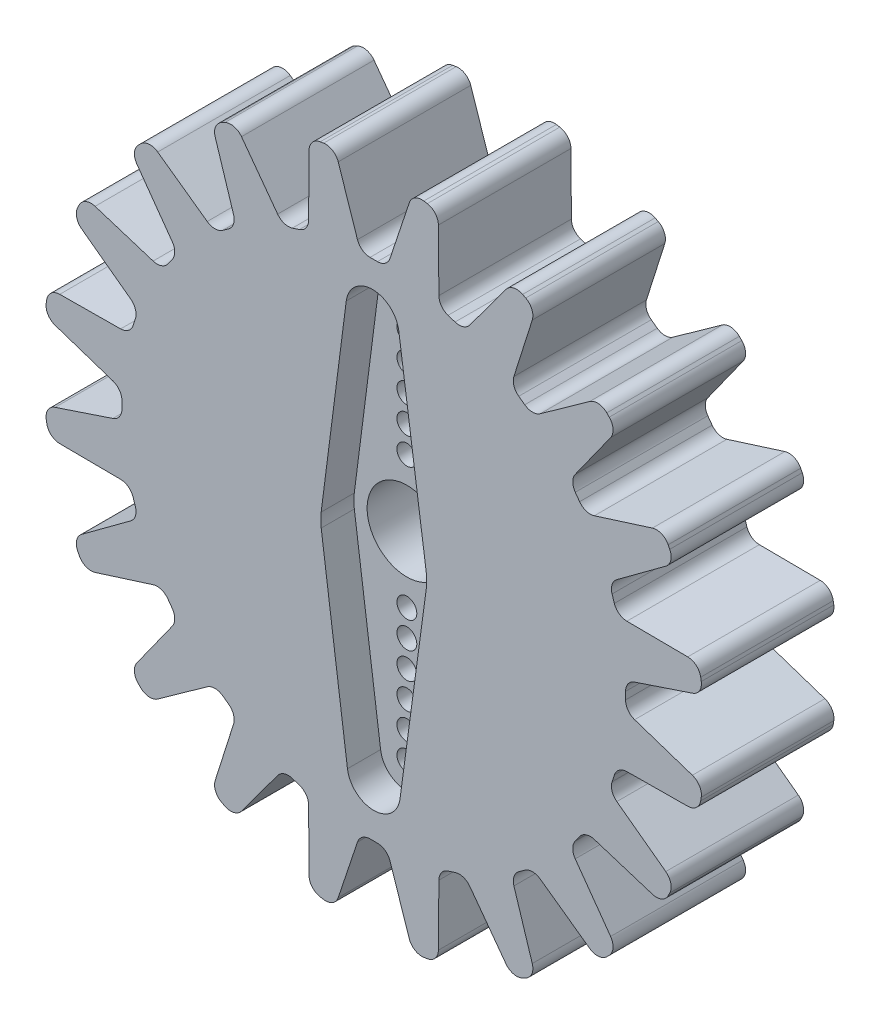
SolidWorks part; units mm, degrees
ref_plane "Front Plane" through (0, 0, 0) normal (0, 0, 1) x (1, 0, 0)
ref_plane "Top Plane" through (0, 0, 0) normal (0, 1, 0) x (1, 0, 0)
ref_plane "Right Plane" through (0, 0, 0) normal (1, 0, 0) x (0, 0, -1)
sketch "Sketch1" plane through (0, 0, 0) normal (0, 0, 1) x (1, 0, 0)
  circle A0 centre (0, 0) radius 25
  dimension "D1" = 50
extrude "Boss-Extrude1" add sketch "Sketch1" along normal blind 10
sketch "Sketch4" plane through (0, 0, 10) normal (0, 0, 1) x (1, 0, 0)
  line L0 (0, 25) -> (0, 19)
  line L1 (-1, 19) -> (1, 19)
  line L2 (-3, 25) -> (3, 25)
  line L3 (-3, 25) -> (-1, 19)
  line L4 (1, 19) -> (3, 25)
  circle A0 centre (0, 0) radius 25 construction
  point P9 (0, 19)
  point P12 (0, 25)
  point P13 (0, 25)
  circle M4 centre (0, 0) radius 25
  dimension "D1" = 6
  dimension "D2" = 2
  dimension "D3" = 6
extrude "Cut-Extrude1" cut sketch "Sketch4" against normal blind 15 contours L3 L1 L0 M4 | L1 L4 L0 M4 region at (1.0664, 22.4637, 10) region at (-1.0664, 22.4637, 10)
ref_axis "Axis1" through (0, 0, 10) along (0, 0, -1)
fillet "Fillet2" radius 1 4 edges at (1, 19, 5) (-1, 19, 5) (2.9421, 24.8263, 5) (-2.9421, 24.8263, 5)
pattern_circular "CirPattern3" count 20 over 360 about axis through (0, 0, 10) along (0, 0, -1) of "Fillet2", "Cut-Extrude1"
sketch "Sketch9" plane through (0, 0, 10) normal (0, 0, 1) x (1, 0, 0)
  circle A0 centre (0, 0) radius 22
sketch "Sketch10" plane through (0, 0, 10) normal (0, 0, 1) x (1, 0, 0)
  line L0 (1.8908, 15.2783) -> (3.961, 0.557)
  line L1 (-3.9643, -0.5333) -> (-1.9821, -15.2667)
  line L2 (1.9821, -15.2667) -> (3.9643, -0.5333)
  line L3 (-3.9674, 0.5096) -> (-2.0734, 15.2545)
  circle A0 centre (-0.0897, 14.9997) radius 2
  circle A1 centre (0, -15) radius 2
  circle A2 centre (0, 0) radius 4
  dimension "D1" = 4
  dimension "D2" = 4
  dimension "D3" = 8
  dimension "D4" = 15
  dimension "D5" = 15
extrude "Cut-Extrude2" cut sketch "Sketch10" against normal blind 2.5 contours A2 A0 | A2 | A2 A1 | A0 | A1 region at (-0.0477, 7.9795, 10) region at (0, 0, 10) region at (0, -7.9796, 10)
sketch "Sketch11" plane through (0, 0, 7.5) normal (0, 0, 1) x (1, 0, 0)
  circle A0 centre (0, 0) radius 3
  circle A3 centre (0, 5) radius 0.75
  circle A4 centre (0, -5) radius 0.75
  circle A6 centre (0, 7) radius 0.75
  circle A7 centre (0, 9) radius 0.75
  circle A8 centre (0, 11) radius 0.75
  circle A9 centre (0, 13) radius 0.75
  circle A10 centre (0, 15) radius 0.75
  circle A11 centre (0, -7) radius 0.75
  circle A12 centre (0, -9) radius 0.75
  circle A13 centre (0, -11) radius 0.75
  circle A14 centre (0, -13) radius 0.75
  circle A15 centre (0, -15) radius 0.75
  dimension "D1" = 6
  dimension "D2" = 6
extrude "Cut-Extrude3" cut sketch "Sketch11" against normal through all both and the other way through all
